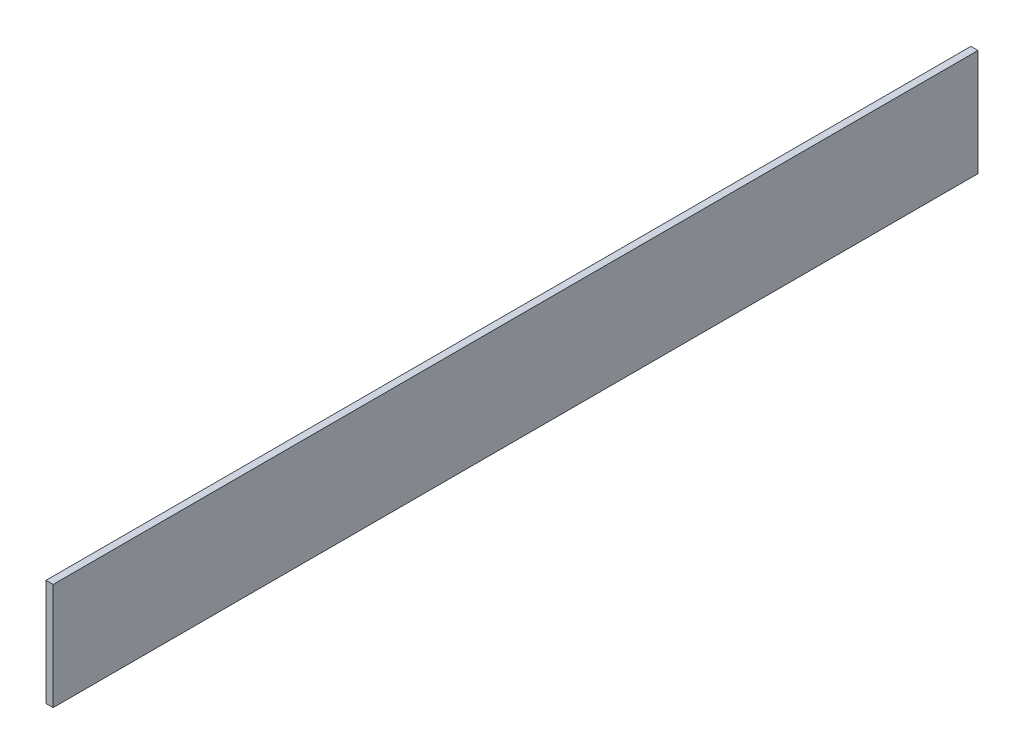
SolidWorks part; units mm, degrees
ref_plane "Ebene vorne" through (0, 0, 0) normal (0, 0, 1) x (1, 0, 0)
ref_plane "Ebene oben" through (0, 0, 0) normal (0, 1, 0) x (1, 0, 0)
ref_plane "Ebene rechts" through (0, 0, 0) normal (1, 0, 0) x (0, 0, -1)
sketch "Skizze1" plane through (0, 20, 0) normal (0, 1, 0) x (1, 0, 0)
  line L0 (150, 75) -> (150, -55)
extrude "Linear-Austragen-Dünn1" add sketch "Skizze1" along normal blind 15 thin thin type one direction wall 1
